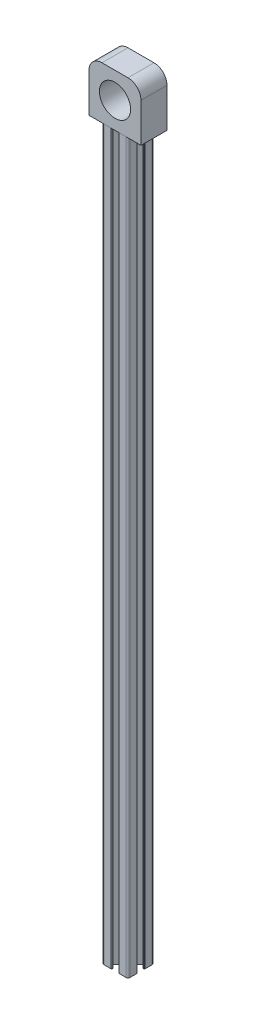
SolidWorks part; units mm, degrees
material "6061-O (SS)"
ref_plane "Front Plane" through (0, 0, 0) normal (0, 0, 1) x (1, 0, 0)
ref_plane "Top Plane" through (0, 0, 0) normal (0, 1, 0) x (1, 0, 0)
ref_plane "Right Plane" through (0, 0, 0) normal (1, 0, 0) x (0, 0, -1)
sketch "Sketch1" plane through (0, 0, 0) normal (0, 1, 0) x (1, 0, 0)
  line L0 (9.4949, 2.6581) -> (9.0109, 2.6581)
  line L1 (8.5029, 3.1661) -> (8.5029, 5.5151)
  line L2 (10.0029, 3.1661) -> (10.0029, 8.5281)
  line L3 (3.6579, -2.3558) -> (3.6579, 2.412)
  line L4 (7.269, 6.0231) -> (7.9949, 6.0231)
  line L5 (6.9098, 5.8743) -> (3.8067, 2.7712)
  line L6 (9.4949, -2.6019) -> (9.0109, -2.6019)
  line L7 (10.0029, -3.1099) -> (10.0029, -8.4719)
  line L8 (8.5029, -3.1099) -> (8.5029, -5.4589)
  line L9 (7.269, -5.9669) -> (7.9949, -5.9669)
  line L10 (6.9098, -5.8181) -> (3.8067, -2.715)
  line L11 (2.1278, -2.2764) -> (2.3074, -2.0968)
  line L12 (-2.6271, 9.5201) -> (-2.6271, 9.0361)
  line L13 (-3.1351, 10.0281) -> (-8.4971, 10.0281)
  line L14 (-3.1351, 8.5281) -> (-5.4841, 8.5281)
  line L15 (2.3868, 3.6831) -> (-2.381, 3.6831)
  line L16 (-5.9921, 7.2942) -> (-5.9921, 8.0201)
  line L17 (-5.8433, 6.935) -> (-2.7402, 3.8319)
  line L18 (2.6329, 9.5201) -> (2.6329, 9.0361)
  line L19 (3.1409, 10.0281) -> (8.5029, 10.0281)
  line L20 (3.1409, 8.5281) -> (5.4899, 8.5281)
  line L21 (5.9979, 7.2942) -> (5.9979, 8.0201)
  line L22 (5.8491, 6.935) -> (2.746, 3.8319)
  line L23 (2.3074, 2.153) -> (2.1278, 2.3326)
  line L24 (-9.4891, -2.6019) -> (-9.0051, -2.6019)
  line L25 (-9.9971, -3.1099) -> (-9.9971, -8.4719)
  line L26 (-8.4971, -3.1099) -> (-8.4971, -5.4589)
  line L27 (-3.6521, 2.412) -> (-3.6521, -2.3558)
  line L28 (-7.2632, -5.9669) -> (-7.9891, -5.9669)
  line L29 (-6.904, -5.8181) -> (-3.8009, -2.715)
  line L30 (-9.4891, 2.6581) -> (-9.0051, 2.6581)
  line L31 (-9.9971, 3.1661) -> (-9.9971, 8.5281)
  line L32 (-8.4971, 3.1661) -> (-8.4971, 5.5151)
  line L33 (-7.2632, 6.0231) -> (-7.9891, 6.0231)
  line L34 (-6.904, 5.8743) -> (-3.8009, 2.7712)
  line L35 (-2.122, 2.3326) -> (-2.3016, 2.153)
  line L36 (2.6329, -9.4639) -> (2.6329, -8.9799)
  line L37 (3.1409, -9.9719) -> (8.5029, -9.9719)
  line L38 (3.1409, -8.4719) -> (5.4899, -8.4719)
  line L39 (-2.381, -3.6269) -> (2.3868, -3.6269)
  line L40 (5.9979, -7.238) -> (5.9979, -7.9639)
  line L41 (5.8491, -6.8788) -> (2.746, -3.7757)
  line L42 (-2.6271, -9.4639) -> (-2.6271, -8.9799)
  line L43 (-3.1351, -9.9719) -> (-8.4971, -9.9719)
  line L44 (-3.1351, -8.4719) -> (-5.4841, -8.4719)
  line L45 (-5.9921, -7.238) -> (-5.9921, -7.9639)
  line L46 (-5.8433, -6.8788) -> (-2.7402, -3.7757)
  line L47 (-2.3016, -2.0968) -> (-2.122, -2.2764)
  arc A0 (-0.8011, -1.9071) -> (0.8069, -1.9071) centre (0.0029, 0.0281) ccw
  arc A1 (8.5029, 5.5151) -> (7.9949, 6.0231) centre (7.9949, 5.5151) ccw
  arc A2 (7.269, 6.0231) -> (6.9098, 5.8743) centre (7.269, 5.5151) ccw
  arc A3 (3.8067, 2.7712) -> (3.6579, 2.412) centre (4.1659, 2.412) ccw
  arc A4 (3.6579, -2.3558) -> (3.8067, -2.715) centre (4.1659, -2.3558) ccw
  arc A5 (6.9098, -5.8181) -> (7.269, -5.9669) centre (7.269, -5.4589) ccw
  arc A6 (7.9949, -5.9669) -> (8.5029, -5.4589) centre (7.9949, -5.4589) ccw
  arc A7 (9.0109, -2.6019) -> (8.5029, -3.1099) centre (9.0109, -3.1099) ccw
  arc A8 (10.0029, -3.1099) -> (9.4949, -2.6019) centre (9.4949, -3.1099) ccw
  arc A9 (9.4949, 2.6581) -> (10.0029, 3.1661) centre (9.4949, 3.1661) ccw
  arc A10 (8.5029, 3.1661) -> (9.0109, 2.6581) centre (9.0109, 3.1661) ccw
  arc A11 (0.8069, -1.9071) -> (2.1278, -2.2764) centre (1.5713, -1.7199) ccw
  arc A12 (2.3074, -2.0968) -> (1.9381, -0.7759) centre (1.7509, -1.5403) ccw
  arc A13 (-2.6271, 9.5201) -> (-3.1351, 10.0281) centre (-3.1351, 9.5201) ccw
  arc A14 (-3.1351, 8.5281) -> (-2.6271, 9.0361) centre (-3.1351, 9.0361) ccw
  arc A15 (1.9381, -0.7759) -> (1.9381, 0.8321) centre (0.0029, 0.0281) ccw
  arc A16 (-2.7402, 3.8319) -> (-2.381, 3.6831) centre (-2.381, 4.1911) ccw
  arc A17 (-5.4841, 8.5281) -> (-5.9921, 8.0201) centre (-5.4841, 8.0201) ccw
  arc A18 (-5.9921, 7.2942) -> (-5.8433, 6.935) centre (-5.4841, 7.2942) ccw
  arc A19 (2.6329, 9.0361) -> (3.1409, 8.5281) centre (3.1409, 9.0361) ccw
  arc A20 (3.1409, 10.0281) -> (2.6329, 9.5201) centre (3.1409, 9.5201) ccw
  arc A21 (5.9979, 8.0201) -> (5.4899, 8.5281) centre (5.4899, 8.0201) ccw
  arc A22 (5.8491, 6.935) -> (5.9979, 7.2942) centre (5.4899, 7.2942) ccw
  arc A23 (2.3868, 3.6831) -> (2.746, 3.8319) centre (2.3868, 4.1911) ccw
  arc A24 (1.9381, 0.8321) -> (2.3074, 2.153) centre (1.7509, 1.5965) ccw
  arc A25 (2.1278, 2.3326) -> (0.8069, 1.9632) centre (1.5713, 1.7761) ccw
  arc A26 (-9.4891, -2.6019) -> (-9.9971, -3.1099) centre (-9.4891, -3.1099) ccw
  arc A27 (-8.4971, -3.1099) -> (-9.0051, -2.6019) centre (-9.0051, -3.1099) ccw
  arc A28 (0.8069, 1.9632) -> (-0.8011, 1.9632) centre (0.0029, 0.0281) ccw
  arc A29 (-3.8009, -2.715) -> (-3.6521, -2.3558) centre (-4.1601, -2.3558) ccw
  arc A30 (-8.4971, -5.4589) -> (-7.9891, -5.9669) centre (-7.9891, -5.4589) ccw
  arc A31 (-7.2632, -5.9669) -> (-6.904, -5.8181) centre (-7.2632, -5.4589) ccw
  arc A32 (-9.0051, 2.6581) -> (-8.4971, 3.1661) centre (-9.0051, 3.1661) ccw
  arc A33 (-9.9971, 3.1661) -> (-9.4891, 2.6581) centre (-9.4891, 3.1661) ccw
  arc A34 (-7.9891, 6.0231) -> (-8.4971, 5.5151) centre (-7.9891, 5.5151) ccw
  arc A35 (-6.904, 5.8743) -> (-7.2632, 6.0231) centre (-7.2632, 5.5151) ccw
  arc A36 (-3.6521, 2.412) -> (-3.8009, 2.7712) centre (-4.1601, 2.412) ccw
  arc A37 (-0.8011, 1.9632) -> (-2.122, 2.3326) centre (-1.5655, 1.7761) ccw
  arc A38 (-2.3016, 2.153) -> (-1.9322, 0.8321) centre (-1.7451, 1.5965) ccw
  arc A39 (2.6329, -9.4639) -> (3.1409, -9.9719) centre (3.1409, -9.4639) ccw
  arc A40 (3.1409, -8.4719) -> (2.6329, -8.9799) centre (3.1409, -8.9799) ccw
  arc A41 (-1.9322, 0.8321) -> (-1.9322, -0.7759) centre (0.0029, 0.0281) ccw
  arc A42 (2.746, -3.7757) -> (2.3868, -3.6269) centre (2.3868, -4.1349) ccw
  arc A43 (5.4899, -8.4719) -> (5.9979, -7.9639) centre (5.4899, -7.9639) ccw
  arc A44 (5.9979, -7.238) -> (5.8491, -6.8788) centre (5.4899, -7.238) ccw
  arc A45 (-2.6271, -8.9799) -> (-3.1351, -8.4719) centre (-3.1351, -8.9799) ccw
  arc A46 (-3.1351, -9.9719) -> (-2.6271, -9.4639) centre (-3.1351, -9.4639) ccw
  arc A47 (-5.9921, -7.9639) -> (-5.4841, -8.4719) centre (-5.4841, -7.9639) ccw
  arc A48 (-5.8433, -6.8788) -> (-5.9921, -7.238) centre (-5.4841, -7.238) ccw
  arc A49 (-2.381, -3.6269) -> (-2.7402, -3.7757) centre (-2.381, -4.1349) ccw
  arc A50 (-1.9322, -0.7759) -> (-2.3016, -2.0968) centre (-1.7451, -1.5403) ccw
  arc A51 (-2.122, -2.2764) -> (-0.8011, -1.9071) centre (-1.5655, -1.7199) ccw
  arc A52 (10.0029, 8.5281) -> (8.5029, 10.0281) centre (8.5029, 8.5281) ccw
  arc A53 (8.5029, -9.9719) -> (10.0029, -8.4719) centre (8.5029, -8.4719) ccw
  arc A54 (-9.9971, -8.4719) -> (-8.4971, -9.9719) centre (-8.4971, -8.4719) ccw
  arc A55 (-8.4971, 10.0281) -> (-9.9971, 8.5281) centre (-8.4971, 8.5281) ccw
extrude "Boss-Extrude1" add sketch "Sketch1" along normal blind 560
sketch "Sketch2" plane through (0, 560, 0) normal (0, 1, 0) x (1, 0, 0)
  line L1 (-20, -10) -> (20, -10)
  line L2 (-20, -10) -> (-20, 10)
  line L3 (-20, 10) -> (20, 10)
  line L4 (20, -10) -> (20, 10)
  line L5 (-20, -10) -> (20, 10) construction
  line L6 (-20, 10) -> (20, -10) construction
  point P0 (0, 0)
  dimension "D1" = 20
extrude "Boss-Extrude2" add sketch "Sketch2" along normal blind 40
fillet "Fillet1" radius 10 2 edges at (-20, 600, 0) (20, 600, 0)
sketch "Sketch3" plane through (0, 0, 10) normal (0, 0, 1) x (1, 0, 0)
  line L0 (0, 560) -> (0, 600) construction
  line L3 (-20, 560) -> (20, 560) construction
  line L4 (-10, 600) -> (10, 600) construction
  circle A0 centre (0, 580) radius 12
  dimension "D1" = 24
extrude "Cut-Extrude1" cut sketch "Sketch3" against normal blind 40
